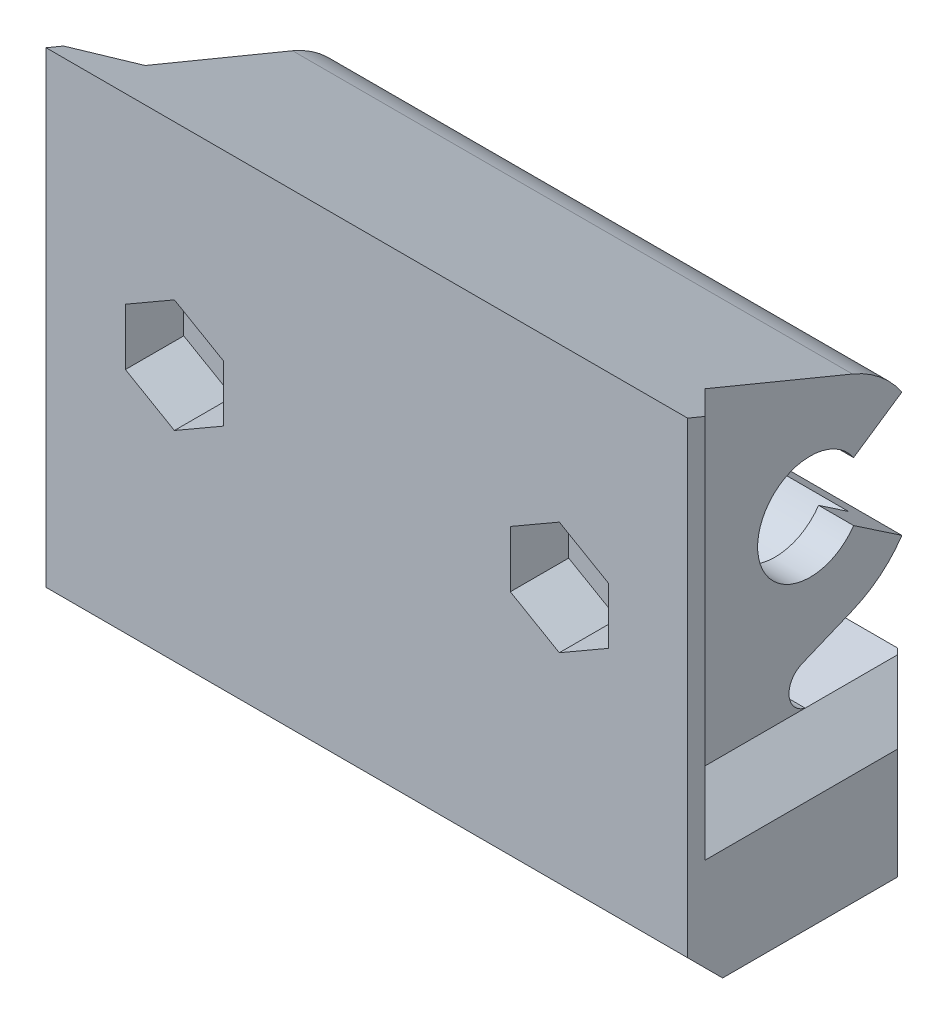
SolidWorks part; units mm, degrees
ref_plane "Front Plane" through (0, 0, 0) normal (0, 0, 1) x (1, 0, 0)
ref_plane "Top Plane" through (0, 0, 0) normal (0, 1, 0) x (1, 0, 0)
ref_plane "Right Plane" through (0, 0, 0) normal (1, 0, 0) x (0, 0, -1)
sketch "Sketch1" plane through (0, 0, 0) normal (0, 0, 1) x (1, 0, 0)
  line L1 (-10.3542, -6.2205) -> (44.6458, -6.2205)
  line L2 (-10.3542, -6.2205) -> (-10.3542, 38.7795)
  line L3 (-10.3542, 38.7795) -> (44.6458, 38.7795)
  line L4 (44.6458, -6.2205) -> (44.6458, 38.7795)
  dimension "D1" = 55
  dimension "D2" = 45
extrude "Boss-Extrude1" add sketch "Sketch1" along normal blind 5 contours L3 L4 L1 L2
sketch "Sketch3" plane through (0, 0, 0) normal (0, 0, -1) x (-1, 0, 0)
  line L0 (10.3542, -6.2205) -> (10.3542, 38.7795) construction
  line L1 (-44.6458, -6.2205) -> (10.3542, -6.2205)
  line L2 (-44.6458, -6.2205) -> (-44.6458, 6.7795)
  line L3 (-44.6458, 6.7795) -> (10.3542, 6.7795)
  line L4 (10.3542, -6.2205) -> (10.3542, 6.7795)
  dimension "D1" = 13
extrude "Boss-Extrude5" add sketch "Sketch3" along normal blind 20 contours L3 L4 L1 L2
chamfer "Chamfer1" distance 3 angle 45 1 edges at (17.1458, -6.2205, 5)
sketch "Sketch5" plane through (0, -6.2205, 0) normal (0, -1, 0) x (1, 0, 0)
  line L0 (44.6458, -20) -> (-10.3542, -20) construction
  line L1 (-10.3542, 2) -> (-10.3542, -20) construction
  circle A0 centre (-0.3542, -7) radius 4.2
  circle A1 centre (34.6458, -7) radius 4.2
  dimension "D1" = 35
  dimension "D2" = 13
  dimension "D3" = 10
extrude "Cut-Extrude2" cut sketch "Sketch5" against normal blind 8
sketch "Sketch6" plane through (-10.3542, 0, 0) normal (-1, 0, 0) x (0, 0, 1)
  line L0 (0, 6.7795) -> (0, 38.7795) construction
  line L1 (-20, 6.7795) -> (0, 6.7795) construction
  line L2 (-8.3082, 10.2139) -> (-12.6292, 12.0001)
  line L3 (-18.5, 20.7795) -> (-16.45, 20.7795) construction
  line L4 (0, 34.7795) -> (-12.6292, 29.559)
  line L5 (-16.1429, 18.6625) -> (-18.1084, 18.08)
  line L6 (-16.1429, 22.8965) -> (-18.1084, 23.479)
  line L7 (0, 34.7795) -> (0, 6.7795)
  line L8 (-1.55, 20.7795) -> (7.8073, 20.7795) construction
  line L10 (0, 6.7795) -> (-8.5765, 6.7795)
  arc A0 (-16.1429, 18.6625) -> (-16.1429, 22.8965) centre (-9, 20.7795) ccw
  arc A1 (-18.1084, 18.08) -> (-12.6292, 12.0001) centre (-9, 20.7795) ccw
  arc A2 (-12.6292, 29.559) -> (-18.1084, 23.479) centre (-9, 20.7795) ccw
  arc A3 (-8.5765, 6.7795) -> (-8.3082, 10.2139) centre (-9, 8.5403) ccw
  dimension "D1" = 9
  dimension "D2" = 14
ref_plane "Plane1" through (-6.8542, 0, 0) normal (-1, 0, 0) x (0, 0, 1)
sketch "Sketch7" plane through (-6.8542, 0, 0) normal (-1, 0, 0) x (0, 0, 1)
  line L1 (-20, 6.7795) -> (0, 6.7795) construction
  line B0 (-8.3082, 10.2139) -> (-12.6292, 12.0001)
  line B1 (-18.5, 20.7795) -> (-16.45, 20.7795) construction
  line B2 (0, 34.7795) -> (-12.6292, 29.559)
  line B3 (0, 34.7795) -> (0, 6.7795)
  line B4 (0, 6.7795) -> (-8.5765, 6.7795)
  arc B5 (-15.2952, 16.5216) -> (-15.2952, 25.0375) centre (-9, 20.7795) ccw
  arc B6 (-16.869, 15.4571) -> (-12.6292, 12.0001) centre (-9, 20.7795) ccw
  arc B7 (-12.6292, 29.559) -> (-16.869, 26.102) centre (-9, 20.7795) ccw
  arc B8 (-8.5765, 6.7795) -> (-8.3082, 10.2139) centre (-9, 8.5403) ccw
  line B9 (-15.2952, 16.5216) -> (-16.869, 15.4571)
  line B10 (-15.2952, 25.0375) -> (-16.869, 26.102)
sketch_block_instance "Block1-1"
sketch_block "Block1" parameters "D1"=7.45
extrude "Boss-Extrude7" add sketch "Sketch7" against normal blind 48
sketch "Sketch8" plane through (-10.3542, 0, 0) normal (-1, 0, 0) x (0, 0, 1)
  line L0 (0, 34.7795) -> (5, 36.8464)
  line L1 (5, -3.2205) -> (5, 38.7795) construction
  line L2 (0, 34.7795) -> (-12.6292, 29.559) construction
  line L3 (5, 36.8464) -> (5, 38.7795)
  line L4 (5, 38.7795) -> (0, 38.7795)
  line L5 (0, 38.7795) -> (0, 34.7795)
extrude "Cut-Extrude3" cut sketch "Sketch8" against normal through all
chamfer "Chamfer2" distance 3.5 angle 45 2 edges at (-10.3542, 6.7795, -10) (-10.3542, 20.7795, 0)
chamfer "Chamfer3" distance 3.5 angle 45 2 edges at (44.6458, 20.7795, 0) (44.6458, 6.7795, -10)
chamfer "Chamfer4" distance 7 angle 45 2 edges at (44.6458, -1.4705, -20) (-10.3542, -1.4705, -20)
sketch "Sketch9" plane through (41.1458, 0, 0) normal (1, 0, 0) x (0, 0, -1)
  line L0 (15.2952, 16.5216) -> (12.7274, 18.2584)
  line L1 (15.2952, 25.0375) -> (12.7274, 23.3007)
  arc A0 (15.2952, 25.0375) -> (15.2952, 16.5216) centre (9, 20.7795) ccw
  arc A1 (12.7274, 23.3007) -> (12.7274, 18.2584) centre (9, 20.7795) ccw
extrude "Boss-Extrude8" add sketch "Sketch9" against normal blind 3
chamfer "Chamfer5" distance 6 angle 45 1 edges at (17.1458, -6.2205, -20)
sketch "Sketch10" plane through (0, 0, 5) normal (0, 0, 1) x (1, 0, 0)
  line L0 (-10.3542, -3.2205) -> (-10.3542, 36.8464) construction
  line L1 (33.6458, 13.9298) -> (37.8458, 16.3546)
  line L2 (37.8458, 16.3546) -> (37.8458, 21.2044)
  line L3 (37.8458, 21.2044) -> (33.6458, 23.6293)
  line L4 (33.6458, 23.6293) -> (29.4458, 21.2044)
  line L5 (29.4458, 21.2044) -> (29.4458, 16.3546)
  line L6 (29.4458, 16.3546) -> (33.6458, 13.9298)
  line L7 (0.6458, 13.9298) -> (4.8458, 16.3546)
  line L8 (4.8458, 16.3546) -> (4.8458, 21.2044)
  line L9 (4.8458, 21.2044) -> (0.6458, 23.6293)
  line L10 (0.6458, 23.6293) -> (-3.5542, 21.2044)
  line L11 (-3.5542, 21.2044) -> (-3.5542, 16.3546)
  line L12 (-3.5542, 16.3546) -> (0.6458, 13.9298)
  line L13 (44.6458, -3.2205) -> (44.6458, 36.8464) construction
  line L14 (44.6458, -6.2205) -> (-10.3542, -6.2205) construction
  circle A0 centre (33.6458, 18.7795) radius 4.2 construction
  circle A1 centre (0.6458, 18.7795) radius 4.2 construction
  point P22 (0, 0)
  dimension "D1" = 11
  dimension "D2" = 11
  dimension "D3" = 25
extrude "Cut-Extrude4" cut sketch "Sketch10" against normal blind 5
sketch "Sketch11" plane through (0, 0, -20) normal (0, 0, -1) x (-1, 0, 0)
  line L0 (10.3542, 36.2263) -> (10.3542, 3.2795) construction
  line L1 (-44.6458, -6.2205) -> (10.3542, -6.2205)
  line L2 (-44.6458, -6.2205) -> (-44.6458, 7.479)
  line L3 (-44.6458, 7.479) -> (10.3542, 7.479)
  line L4 (10.3542, -6.2205) -> (10.3542, 7.479)
extrude "Cut-Extrude5" cut sketch "Sketch11" against normal blind 3
